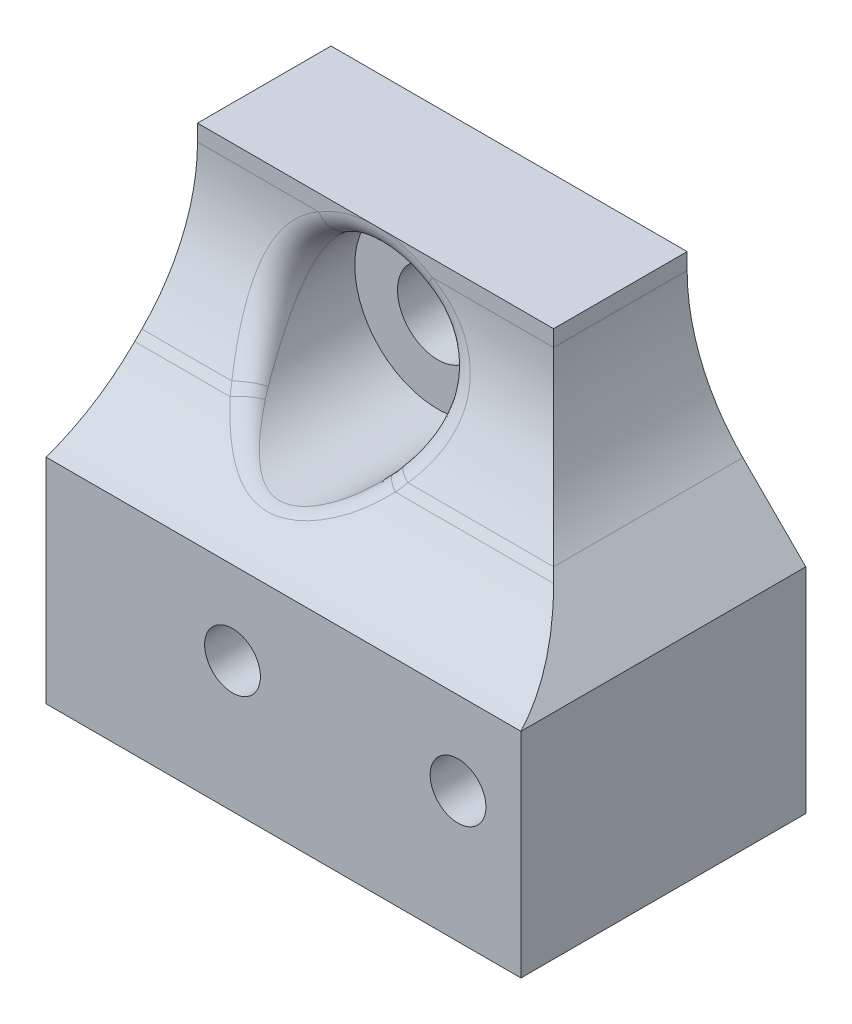
SolidWorks part; units mm, degrees
ref_plane "Front Plane" through (0, 0, 0) normal (0, 0, 1) x (1, 0, 0)
ref_plane "Top Plane" through (0, 0, 0) normal (0, 1, 0) x (1, 0, 0)
ref_plane "Right Plane" through (0, 0, 0) normal (1, 0, 0) x (0, 0, -1)
sketch "Sketch1" plane through (0, 0, 0) normal (0, 0, 1) x (1, 0, 0)
  line L1 (-7.5, 0) -> (12.5, 0)
  line L2 (-7.5, 0) -> (-7.5, 18)
  line L3 (-7.5, 18) -> (12.5, 18)
  line L4 (12.5, 0) -> (12.5, 18)
  dimension "D1" = 7.5
  dimension "D2" = 20
  dimension "D3" = 18
extrude "Boss-Extrude1" add sketch "Sketch1" along normal blind 12
sketch "Sketch2" plane through (0, 0, 12) normal (0, 0, 1) x (1, 0, 0)
  line L0 (-7.5, 18) -> (-7.5, 0) construction
  line L1 (12.5, 18) -> (-7.5, 18) construction
  circle A0 centre (0.35, 5.5) radius 1.175
  circle A1 centre (9.85, 5.5) radius 1.175
  dimension "D1" = 7.85
  dimension "D3" = 2.35
  dimension "D4" = 2.35
  dimension "D2" = 9.5
  dimension "D5" = 12.5
  dimension "D6" = 12.5
extrude "Cut-Extrude1" cut sketch "Sketch2" against normal through all
sketch "Sketch3" plane through (0, 0, 12) normal (0, 0, 1) x (1, 0, 0)
  line L0 (-7.5, 18) -> (-7.5, 0) construction
  line L1 (12.5, 18) -> (7.5, 18)
  line L2 (12.5, 18) -> (12.5, 9)
  line L3 (12.5, 9) -> (7.5, 9)
  line L4 (7.5, 18) -> (7.5, 9)
  dimension "D1" = 15
  dimension "D2" = 9
extrude "Cut-Extrude2" cut sketch "Sketch3" against normal through all
sketch "Sketch4" plane through (0, 0, 12) normal (0, 0, 1) x (1, 0, 0)
  line L1 (-7.5, 18) -> (7.5, 18)
  line L2 (-7.5, 18) -> (-7.5, 9)
  line L3 (-7.5, 9) -> (7.5, 9)
  line L4 (7.5, 18) -> (7.5, 9)
extrude "Cut-Extrude3" cut sketch "Sketch4" against normal blind 6.375
chamfer "Chamfer1" distance 5 angle 45 2 edges at (7.5, 9, 2.8125) (0, 9, 5.625)
fillet "Fillet1" radius 10 1 edges at (2.5, 9, 10.625)
fillet "Fillet2" radius 8 2 edges at (7.5, 14, 2.8125) (0, 14, 5.625)
sketch "Sketch5" plane through (0, 0, 5.625) normal (0, 0, 1) x (1, 0, 0)
  line L0 (7.5, 18) -> (-7.5, 18) construction
  circle A0 centre (0, 13.5) radius 3.5
  dimension "D1" = 7
  dimension "D2" = 4.5
extrude "Cut-Extrude4" cut sketch "Sketch5" against normal offset from surface 3 and the other way through all up to face at (4.8972, 10.5339, 0)
sketch "Sketch6" plane through (0, 0, 3) normal (0, 0, 1) x (1, 0, 0)
  circle A0 centre (0, 13.5) radius 1.7
  dimension "D1" = 3.4
extrude "Cut-Extrude5" cut sketch "Sketch6" against normal through all
fillet "Fillet3" radius 1 4 edges at (-2.8741, 11.5026, 8.1224) (0.2813, 10.0113, 9.9375) (2.8741, 11.5026, 8.1224) (-0.2315, 16.9923, 5.6315)
